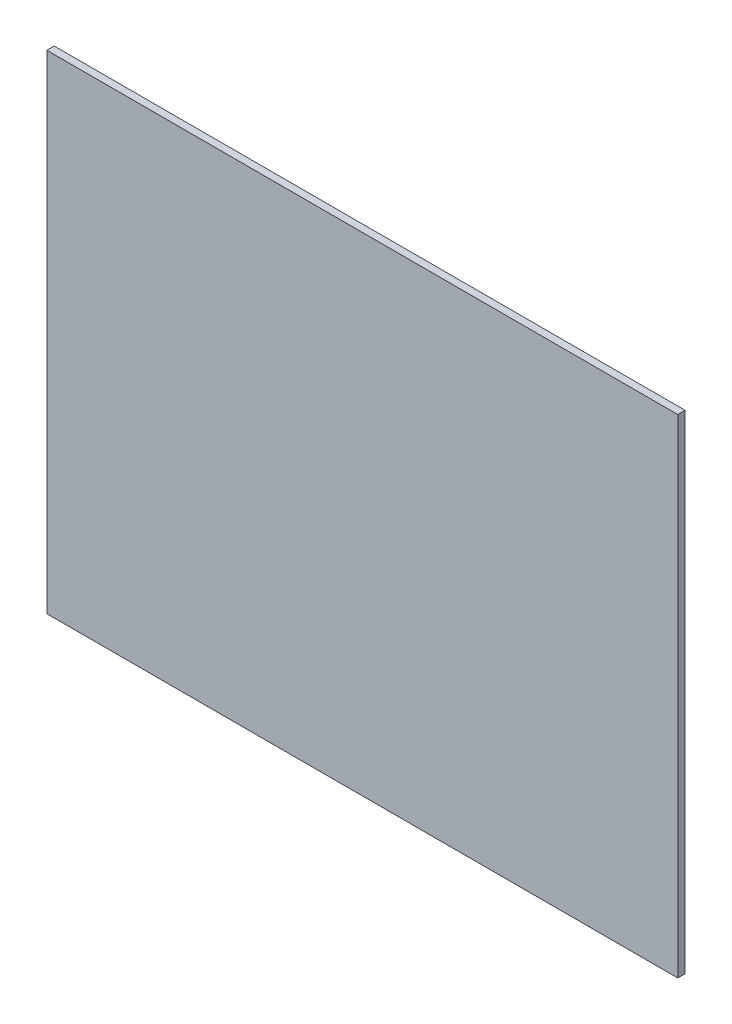
SolidWorks part; units mm, degrees
ref_plane "Спереди" through (0, 0, 0) normal (0, 0, 1) x (1, 0, 0)
ref_plane "Сверху" through (0, 0, 0) normal (0, 1, 0) x (1, 0, 0)
ref_plane "Справа" through (0, 0, 0) normal (1, 0, 0) x (0, 0, -1)
sketch "Эскиз1" plane through (0, 0, 0) normal (0, 0, 1) x (1, 0, 0)
  line L5 (19.5, 16.55) -> (19.5, -16.55)
  line L6 (23.5, 16.75) -> (23.5, 14) construction
  line L14 (23.3, -14) -> (23.3, -16.55)
  line L15 (23.3, -16.55) -> (-23.3, -16.55)
  line L16 (-23.3, -16.55) -> (-23.3, 16.55)
  line L17 (-23.3, 16.55) -> (23.5, 16.55)
  line L19 (19.5, -16.55) -> (-23.3, -16.55)
  line L20 (-23.3, -16.55) -> (-23.3, 16.55)
  line L21 (-23.3, 16.55) -> (19.5, 16.55)
  dimension "D1" = 0.2
  dimension "D2" = 4
extrude "Бобышка-Вытянуть1" add sketch "Эскиз1" along normal blind 0.5 from offset 1.3
